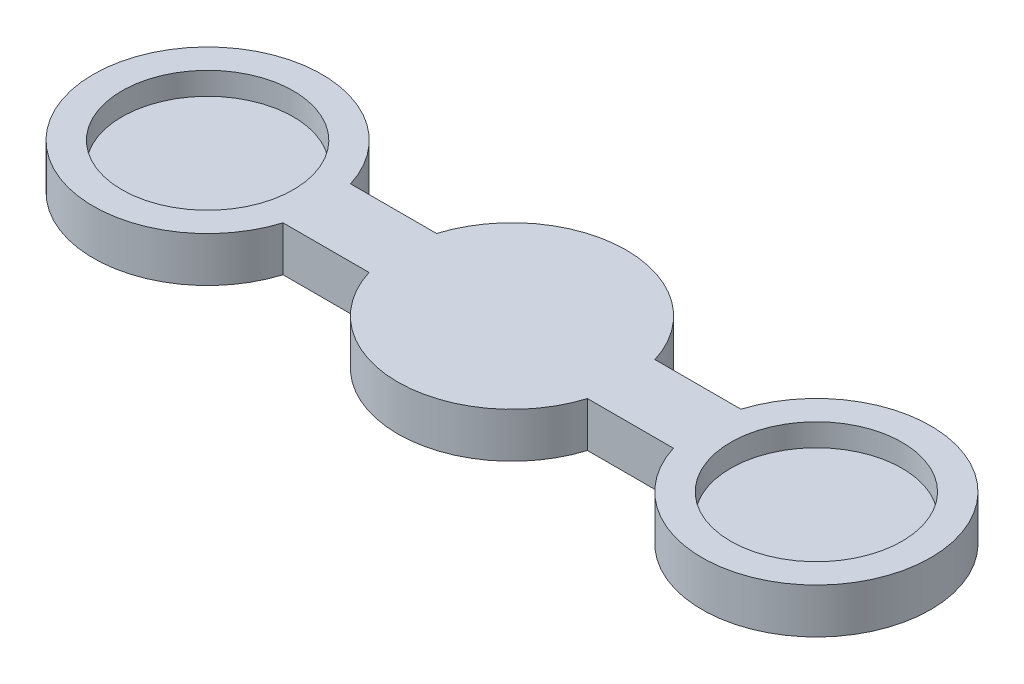
SolidWorks part; units mm, degrees
ref_plane "Front Plane" through (0, 0, 0) normal (0, 0, 1) x (1, 0, 0)
ref_plane "Top Plane" through (0, 0, 0) normal (0, 1, 0) x (1, 0, 0)
ref_plane "Right Plane" through (0, 0, 0) normal (1, 0, 0) x (0, 0, -1)
sketch "Sketch1" plane through (0, 0, 0) normal (0, 1, 0) x (1, 0, 0)
  circle A0 centre (0, 0) radius 12.7
  dimension "D1" = 25.4
extrude "Boss-Extrude1" add sketch "Sketch1" along normal blind 5
sketch "Sketch2" plane through (0, 5, 0) normal (0, 1, 0) x (1, 0, 0)
  line L1 (38.1, -3.75) -> (-38.1, -3.75)
  line L2 (38.1, -3.75) -> (38.1, 3.75)
  line L3 (38.1, 3.75) -> (-38.1, 3.75)
  line L4 (-38.1, -3.75) -> (-38.1, 3.75)
  line L5 (38.1, -3.75) -> (-38.1, 3.75) construction
  line L6 (38.1, 3.75) -> (-38.1, -3.75) construction
  point P0 (0, 0)
  dimension "D1" = 7.5
  dimension "D2" = 76.2
extrude "Boss-Extrude2" add sketch "Sketch2" against normal up to surface (5 mm away) up to face at (0, 0, 12.7)
sketch "Sketch3" plane through (0, 5, 0) normal (0, 1, 0) x (1, 0, 0)
  circle A0 centre (-33.8191, 0) radius 12.7
  dimension "D1" = 25.4
extrude "Boss-Extrude3" add sketch "Sketch3" against normal up to surface (5 mm away) up to face at (0, 0, 0)
sketch "Sketch4" plane through (0, 5, 0) normal (0, 1, 0) x (1, 0, 0)
  circle A0 centre (-33.8191, 0) radius 9.525
  arc A1 (-21.6854, 3.75) -> (-21.6854, -3.75) centre (-33.8191, 0) ccw construction
  dimension "D1" = 19.05
extrude "Cut-Extrude1" cut sketch "Sketch4" against normal blind 2.5
mirror "Mirror1" about plane through (0, 0, 0) normal (1, 0, 0) of "Cut-Extrude1", "Boss-Extrude3"
